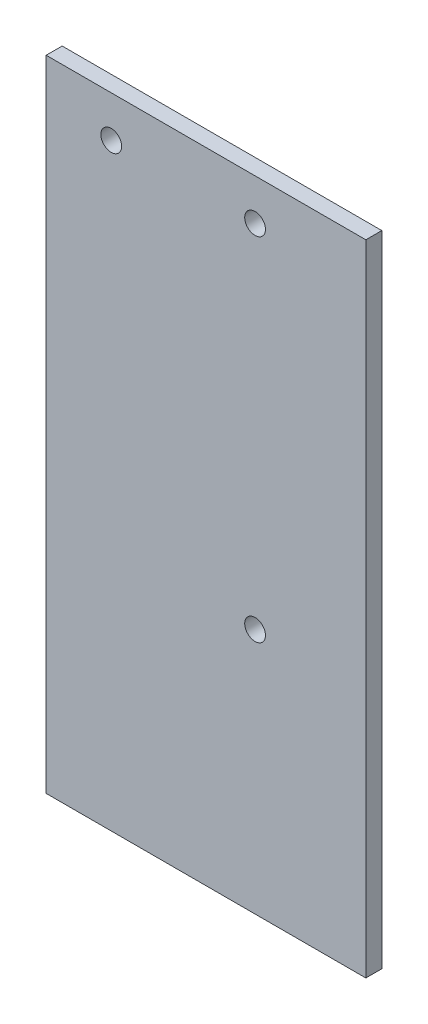
SolidWorks part; units mm, degrees
ref_plane "Front Plane" through (0, 0, 0) normal (1, 0, 0) x (0, 1, 0)
ref_plane "Top Plane" through (0, 0, 0) normal (0, 0, 1) x (0, 1, 0)
ref_plane "Right Plane" through (0, 0, 0) normal (0, 1, 0) x (-1, 0, 0)
sketch "Sketch1" plane through (0, 0, 0) normal (0, 0, 1) x (0, 1, 0)
  line L1 (-50.8, 25.4) -> (50.8, 25.4)
  line L2 (-50.8, 25.4) -> (-50.8, -25.4)
  line L3 (-50.8, -25.4) -> (50.8, -25.4)
  line L4 (50.8, 25.4) -> (50.8, -25.4)
  line L5 (-50.8, 25.4) -> (50.8, -25.4) construction
  line L6 (-50.8, -25.4) -> (50.8, 25.4) construction
  point P0 (0, 0)
  dimension "D1" = 101.6
  dimension "D2" = 50.8
extrude "Boss-Extrude1" add sketch "Sketch1" along normal blind 2.54
sketch "Sketch2" plane through (0, 0, 2.54) normal (0, 0, 1) x (1, 0, 0)
  line L0 (7.7987, -11.6329) -> (7.7987, 44.2471) construction
  line L1 (7.7987, 44.2471) -> (-15.0613, 44.2471) construction
  line L2 (-15.0613, 44.2471) -> (-15.0613, -11.6329) construction
  line L3 (-15.0613, -11.6329) -> (7.7987, -11.6329) construction
  circle A0 centre (7.7987, 44.2471) radius 1.651
  circle A1 centre (7.7987, -11.6329) radius 1.651
  circle A2 centre (-15.0613, 44.2471) radius 1.651
  dimension "D3" = 3.302
  dimension "D1" = 55.88
  dimension "D2" = 22.86
extrude "Cut-Extrude1" cut sketch "Sketch2" against normal through all
